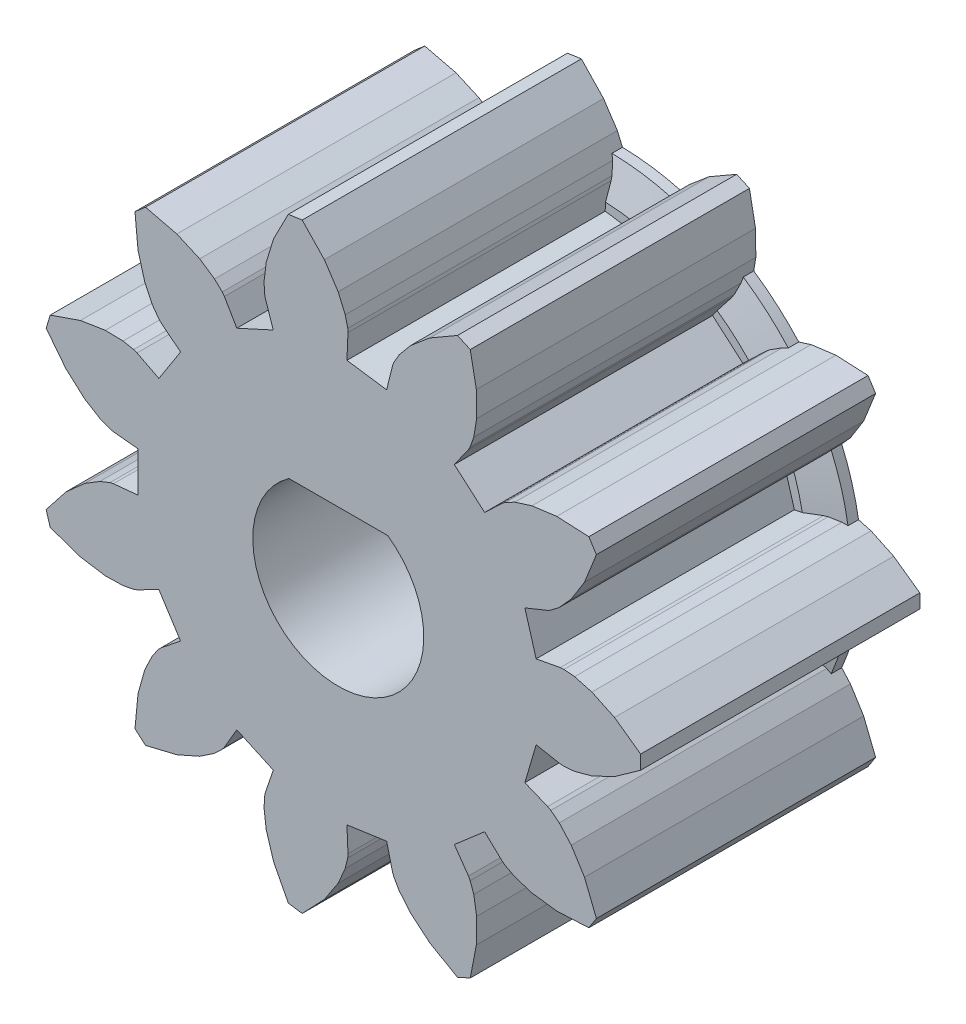
SolidWorks part; units mm, degrees
material "Custom Plastic"
ref_plane "Front Plane" through (0, 0, 0) normal (0, 0, 1) x (1, 0, 0)
ref_plane "Top Plane" through (0, 0, 0) normal (0, 1, 0) x (1, 0, 0)
ref_plane "Right Plane" through (0, 0, 0) normal (1, 0, 0) x (0, 0, -1)
sketch "Model" plane through (0, 0, 0) normal (0, 0, 1) x (1, 0, 0)
  line L0 (-8.37, -2.248) -> (-7.801, -1.524)
  line L1 (-7.801, -1.524) -> (-7.265, -1.048)
  line L2 (-7.265, -1.048) -> (-6.829, -0.78)
  line L3 (-6.829, -0.78) -> (-6.543, -0.667)
  line L4 (-6.543, -0.667) -> (-6.442, -0.645)
  line L5 (-6.442, -0.645) -> (-5.741, -0.575)
  line L6 (-5.741, -0.575) -> (-5.741, 0.575)
  line L7 (-5.741, 0.575) -> (-6.442, 0.645)
  line L8 (-6.442, 0.645) -> (-6.543, 0.667)
  line L9 (-6.543, 0.667) -> (-6.829, 0.78)
  line L10 (-6.829, 0.78) -> (-7.265, 1.048)
  line L11 (-7.265, 1.048) -> (-7.801, 1.524)
  line L12 (-7.801, 1.524) -> (-8.37, 2.248)
  line L13 (-8.37, 2.248) -> (-8.256, 2.634)
  line L14 (-8.256, 2.634) -> (-7.386, 2.935)
  line L15 (-7.386, 2.935) -> (-6.678, 3.046)
  line L16 (-6.678, 3.046) -> (-6.167, 3.035)
  line L17 (-6.167, 3.035) -> (-5.865, 2.976)
  line L18 (-5.865, 2.976) -> (-5.768, 2.94)
  line L19 (-5.768, 2.94) -> (-5.14, 2.62)
  line L20 (-5.14, 2.62) -> (-4.518, 3.587)
  line L21 (-4.518, 3.587) -> (-5.071, 4.026)
  line L22 (-5.071, 4.026) -> (-5.143, 4.099)
  line L23 (-5.143, 4.099) -> (-5.323, 4.348)
  line L24 (-5.323, 4.348) -> (-5.545, 4.81)
  line L25 (-5.545, 4.81) -> (-5.738, 5.5)
  line L26 (-5.738, 5.5) -> (-5.826, 6.416)
  line L27 (-5.826, 6.416) -> (-5.522, 6.679)
  line L28 (-5.522, 6.679) -> (-4.627, 6.462)
  line L29 (-4.627, 6.462) -> (-3.971, 6.173)
  line L30 (-3.971, 6.173) -> (-3.547, 5.887)
  line L31 (-3.547, 5.887) -> (-3.325, 5.674)
  line L32 (-3.325, 5.674) -> (-3.263, 5.592)
  line L33 (-3.263, 5.592) -> (-2.908, 4.983)
  line L34 (-2.908, 4.983) -> (-1.862, 5.461)
  line L35 (-1.862, 5.461) -> (-2.089, 6.128)
  line L36 (-2.089, 6.128) -> (-2.111, 6.229)
  line L37 (-2.111, 6.229) -> (-2.127, 6.536)
  line L38 (-2.127, 6.536) -> (-2.064, 7.044)
  line L39 (-2.064, 7.044) -> (-1.854, 7.729)
  line L40 (-1.854, 7.729) -> (-1.432, 8.547)
  line L41 (-1.432, 8.547) -> (-1.034, 8.604)
  line L42 (-1.034, 8.604) -> (-0.399, 7.938)
  line L43 (-0.399, 7.938) -> (-0.004, 7.34)
  line L44 (-0.004, 7.34) -> (0.199, 6.87)
  line L45 (0.199, 6.87) -> (0.271, 6.571)
  line L46 (0.271, 6.571) -> (0.278, 6.468)
  line L47 (0.278, 6.468) -> (0.248, 5.764)
  line L48 (0.248, 5.764) -> (1.386, 5.601)
  line L49 (1.386, 5.601) -> (1.555, 6.285)
  line L50 (1.555, 6.285) -> (1.592, 6.381)
  line L51 (1.592, 6.381) -> (1.744, 6.648)
  line L52 (1.744, 6.648) -> (2.071, 7.042)
  line L53 (2.071, 7.042) -> (2.619, 7.504)
  line L54 (2.619, 7.504) -> (3.416, 7.965)
  line L55 (3.416, 7.965) -> (3.782, 7.798)
  line L56 (3.782, 7.798) -> (3.956, 6.893)
  line L57 (3.956, 6.893) -> (3.965, 6.177)
  line L58 (3.965, 6.177) -> (3.882, 5.672)
  line L59 (3.882, 5.672) -> (3.78, 5.382)
  line L60 (3.78, 5.382) -> (3.731, 5.291)
  line L61 (3.731, 5.291) -> (3.325, 4.715)
  line L62 (3.325, 4.715) -> (4.194, 3.962)
  line L63 (4.194, 3.962) -> (4.706, 4.446)
  line L64 (4.706, 4.446) -> (4.789, 4.508)
  line L65 (4.789, 4.508) -> (5.062, 4.65)
  line L66 (5.062, 4.65) -> (5.55, 4.804)
  line L67 (5.55, 4.804) -> (6.26, 4.897)
  line L68 (6.26, 4.897) -> (7.18, 4.853)
  line L69 (7.18, 4.853) -> (7.397, 4.515)
  line L70 (7.397, 4.515) -> (7.055, 3.66)
  line L71 (7.055, 3.66) -> (6.675, 3.053)
  line L72 (6.675, 3.053) -> (6.332, 2.673)
  line L73 (6.332, 2.673) -> (6.09, 2.484)
  line L74 (6.09, 2.484) -> (6, 2.434)
  line L75 (6, 2.434) -> (5.347, 2.169)
  line L76 (5.347, 2.169) -> (5.67, 1.066)
  line L77 (5.67, 1.066) -> (6.363, 1.196)
  line L78 (6.363, 1.196) -> (6.466, 1.203)
  line L79 (6.466, 1.203) -> (6.772, 1.175)
  line L80 (6.772, 1.175) -> (7.266, 1.041)
  line L81 (7.266, 1.041) -> (7.914, 0.735)
  line L82 (7.914, 0.735) -> (8.664, 0.201)
  line L83 (8.664, 0.201) -> (8.664, -0.201)
  line L84 (8.664, -0.201) -> (7.914, -0.735)
  line L85 (7.914, -0.735) -> (7.266, -1.041)
  line L86 (7.266, -1.041) -> (6.772, -1.175)
  line L87 (6.772, -1.175) -> (6.466, -1.203)
  line L88 (6.466, -1.203) -> (6.363, -1.196)
  line L89 (6.363, -1.196) -> (5.67, -1.066)
  line L90 (5.67, -1.066) -> (5.346, -2.169)
  line L91 (5.346, -2.169) -> (6, -2.434)
  line L92 (6, -2.434) -> (6.09, -2.484)
  line L93 (6.09, -2.484) -> (6.332, -2.673)
  line L94 (6.332, -2.673) -> (6.675, -3.053)
  line L95 (6.675, -3.053) -> (7.055, -3.66)
  line L96 (7.055, -3.66) -> (7.397, -4.515)
  line L97 (7.397, -4.515) -> (7.18, -4.853)
  line L98 (7.18, -4.853) -> (6.26, -4.897)
  line L99 (6.26, -4.897) -> (5.55, -4.804)
  line L100 (5.55, -4.804) -> (5.062, -4.65)
  line L101 (5.062, -4.65) -> (4.789, -4.508)
  line L102 (4.789, -4.508) -> (4.706, -4.446)
  line L103 (4.706, -4.446) -> (4.194, -3.962)
  line L104 (4.194, -3.962) -> (3.325, -4.715)
  line L105 (3.325, -4.715) -> (3.731, -5.291)
  line L106 (3.731, -5.291) -> (3.78, -5.382)
  line L107 (3.78, -5.382) -> (3.882, -5.672)
  line L108 (3.882, -5.672) -> (3.965, -6.177)
  line L109 (3.965, -6.177) -> (3.956, -6.893)
  line L110 (3.956, -6.893) -> (3.782, -7.798)
  line L111 (3.782, -7.798) -> (3.416, -7.965)
  line L112 (3.416, -7.965) -> (2.619, -7.504)
  line L113 (2.619, -7.504) -> (2.071, -7.042)
  line L114 (2.071, -7.042) -> (1.744, -6.648)
  line L115 (1.744, -6.648) -> (1.592, -6.381)
  line L116 (1.592, -6.381) -> (1.555, -6.285)
  line L117 (1.555, -6.285) -> (1.386, -5.601)
  line L118 (1.386, -5.601) -> (0.248, -5.764)
  line L119 (0.248, -5.764) -> (0.278, -6.468)
  line L120 (0.278, -6.468) -> (0.271, -6.571)
  line L121 (0.271, -6.571) -> (0.199, -6.87)
  line L122 (0.199, -6.87) -> (-0.004, -7.34)
  line L123 (-0.004, -7.34) -> (-0.399, -7.938)
  line L124 (-0.399, -7.938) -> (-1.034, -8.604)
  line L125 (-1.034, -8.604) -> (-1.432, -8.547)
  line L126 (-1.432, -8.547) -> (-1.854, -7.729)
  line L127 (-1.854, -7.729) -> (-2.064, -7.044)
  line L128 (-2.064, -7.044) -> (-2.127, -6.536)
  line L129 (-2.127, -6.536) -> (-2.111, -6.229)
  line L130 (-2.111, -6.229) -> (-2.089, -6.128)
  line L131 (-2.089, -6.128) -> (-1.862, -5.461)
  line L132 (-1.862, -5.461) -> (-2.908, -4.983)
  line L133 (-2.908, -4.983) -> (-3.263, -5.592)
  line L134 (-3.263, -5.592) -> (-3.325, -5.674)
  line L135 (-3.325, -5.674) -> (-3.547, -5.887)
  line L136 (-3.547, -5.887) -> (-3.971, -6.173)
  line L137 (-3.971, -6.173) -> (-4.627, -6.462)
  line L138 (-4.627, -6.462) -> (-5.522, -6.679)
  line L139 (-5.522, -6.679) -> (-5.826, -6.416)
  line L140 (-5.826, -6.416) -> (-5.738, -5.5)
  line L141 (-5.738, -5.5) -> (-5.545, -4.81)
  line L142 (-5.545, -4.81) -> (-5.323, -4.348)
  line L143 (-5.323, -4.348) -> (-5.143, -4.099)
  line L144 (-5.143, -4.099) -> (-5.071, -4.026)
  line L145 (-5.071, -4.026) -> (-4.519, -3.587)
  line L146 (-4.519, -3.587) -> (-5.141, -2.62)
  line L147 (-5.141, -2.62) -> (-5.768, -2.94)
  line L148 (-5.768, -2.94) -> (-5.865, -2.976)
  line L149 (-5.865, -2.976) -> (-6.167, -3.035)
  line L150 (-6.167, -3.035) -> (-6.678, -3.046)
  line L151 (-6.678, -3.046) -> (-7.386, -2.935)
  line L152 (-7.386, -2.935) -> (-8.256, -2.634)
  line L153 (-8.256, -2.634) -> (-8.37, -2.248)
extrude "Boss-Extrude1" add sketch "Model" along normal blind 8
sketch "Sketch2" plane through (0, 0, 8) normal (0, 0, 1) x (1, 0, 0)
  line L0 (0, 0) -> (0, 2) construction
  line L1 (-1.4151, 2) -> (1.4151, 2)
  arc A0 (-1.4151, 2) -> (1.4151, 2) centre (0, 0) ccw
  dimension "D1" = 4.9
  dimension "D2" = 2
extrude "Cut-Extrude1" cut sketch "Sketch2" against normal through all
sketch "Sketch3" plane through (0, 0, 0) normal (0, 1, 0) x (1, 0, 0)
  line L0 (3.2, 0) -> (3.2, -0.6)
  line L1 (3.416, 0) -> (2.619, 0) construction
  line L2 (3.2, -0.6) -> (6, -0.6)
  line L5 (7, 0) -> (3.2, 0)
  line L6 (0, 0) -> (0, -5.7452) construction
  line L7 (7, 0) -> (7, -0.3)
  line L8 (7, -0.3) -> (6, -0.6)
  dimension "D1" = 3.2
  dimension "D2" = 0.3
  dimension "D3" = 0.6
  dimension "D4" = 7
  dimension "D5" = 1
revolve "Revolve1" add sketch "Sketch3" angle 360 about L6
chamfer "Chamfer1" distance 1 angle 30 2 edges at (0, 2, 0) (0, -2.45, 0) first distance on face at (0, 2, 4) first distance on face at (0, -0.225, 4)
